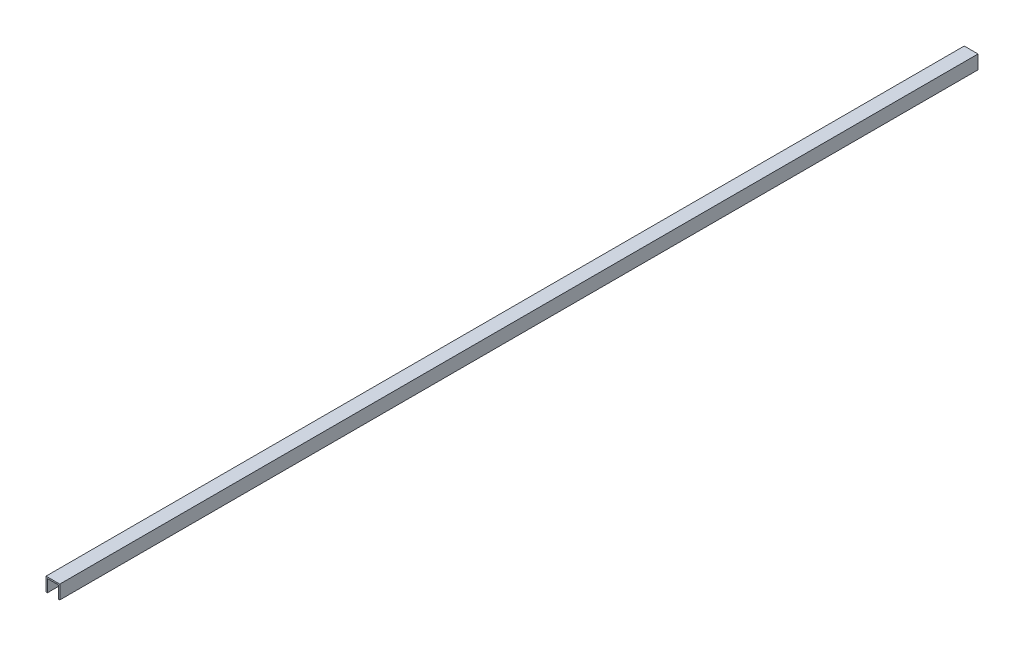
SolidWorks part; units mm, degrees
ref_plane "Спереди" through (0, 0, 0) normal (0, 0, 1) x (1, 0, 0)
ref_plane "Сверху" through (0, 0, 0) normal (0, 1, 0) x (1, 0, 0)
ref_plane "Справа" through (0, 0, 0) normal (1, 0, 0) x (0, 0, -1)
other "Configuration Table"
sketch "Sketch2" plane through (0, 0, 0) normal (0, 0, 1) x (1, 0, 0)
  line L0 (-6, -7.5) -> (-6, 6)
  line L1 (7.5, -7.5) -> (6, -7.5)
  line L2 (7.5, -7.5) -> (7.5, 7.5)
  line L3 (7.5, 7.5) -> (-7.5, 7.5)
  line L4 (-7.5, -7.5) -> (-7.5, 7.5)
  line L5 (7.5, -7.5) -> (-7.5, 7.5) construction
  line L6 (7.5, 7.5) -> (-7.5, -7.5) construction
  line L7 (-6, 6) -> (6, 6)
  line L8 (6, 6) -> (6, -7.5)
  line L9 (0, 7.5) -> (0, -12.4687) construction
  line L10 (-6, -7.5) -> (-7.5, -7.5)
  point P0 (0, 0)
  dimension "D1" = 15
  dimension "D2" = 15
  dimension "D3" = 1.5
  dimension "D4" = 1.5
extrude "Boss-Extrude1" add sketch "Sketch2" along normal mid plane 1000
